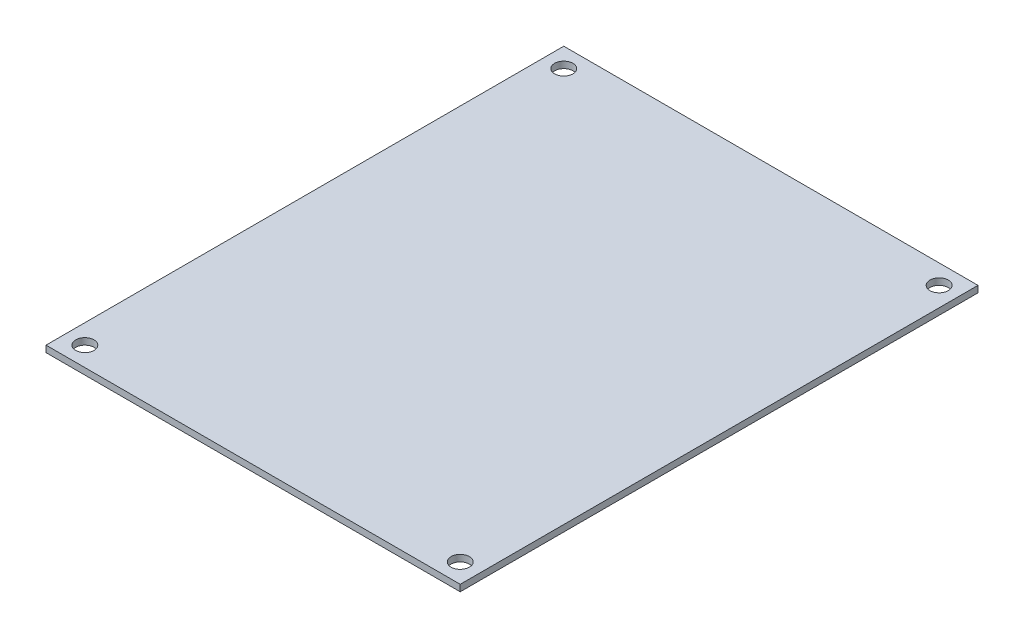
SolidWorks part; units mm, degrees
ref_plane "Front" through (0, 0, 0) normal (0, 0, 1) x (1, 0, 0)
ref_plane "Top" through (0, 0, 0) normal (0, 1, 0) x (1, 0, 0)
ref_plane "Right" through (0, 0, 0) normal (1, 0, 0) x (0, 0, -1)
sketch "Sketch1" plane through (0, 0, 0) normal (0, 1, 0) x (1, 0, 0)
  line L1 (-50.8, -63.5) -> (50.8, -63.5)
  line L2 (-50.8, -63.5) -> (-50.8, 63.5)
  line L3 (-50.8, 63.5) -> (50.8, 63.5)
  line L4 (50.8, -63.5) -> (50.8, 63.5)
  line L5 (-50.8, -63.5) -> (50.8, 63.5) construction
  line L6 (-50.8, 63.5) -> (50.8, -63.5) construction
  point P0 (0, 0)
  dimension "D1" = 127
  dimension "D2" = 101.6
extrude "Boss-Extrude1" add sketch "Sketch1" along normal blind 1.6
hole_wizard "M4 Clearance Hole1" positions "Sketch2" profile "Sketch3" hole size "M4" standard "ANSI Metric"
sketch "Sketch2" plane through (0, 1.6, 0) normal (0, 1, 0) x (1, 0, 0)
  line L1 (-46.0375, 58.7375) -> (46.0375, 58.7375)
  line L2 (-46.0375, 58.7375) -> (-46.0375, -58.7375)
  line L3 (-46.0375, -58.7375) -> (46.0375, -58.7375)
  line L4 (46.0375, 58.7375) -> (46.0375, -58.7375)
  line L5 (-46.0375, 58.7375) -> (46.0375, -58.7375) construction
  line L6 (-46.0375, -58.7375) -> (46.0375, 58.7375) construction
  line L7 (50.8, -63.5) -> (50.8, 63.5) construction
  line L8 (-50.8, -63.5) -> (50.8, -63.5) construction
  point P0 (-46.0375, 58.7375)
  point P2 (46.0375, 58.7375)
  point P4 (46.0375, -58.7375)
  point P6 (-46.0375, -58.7375)
  dimension "D1" = 4.7625
  dimension "D2" = 4.7625
sketch "Sketch3" plane through (-46.0375, 1.6, -58.7375) normal (1, 0, 0) x (0, 0, 1)
  line L0 (0, 0) -> (0, 51.3519)
  line L1 (0, 51.3519) -> (2.25, 50)
  line L2 (2.25, 50) -> (2.25, 0)
  line L5 (2.25, 0) -> (0, 0)
  line L10 (0, 51.3519) -> (-2.25, 50) construction
  line L11 (0, -6.35) -> (0, 107.95) construction
  dimension "Hole Dia." = 4.5
  dimension "Hole Depth" = 50
  dimension "Drill Angle" = 118
